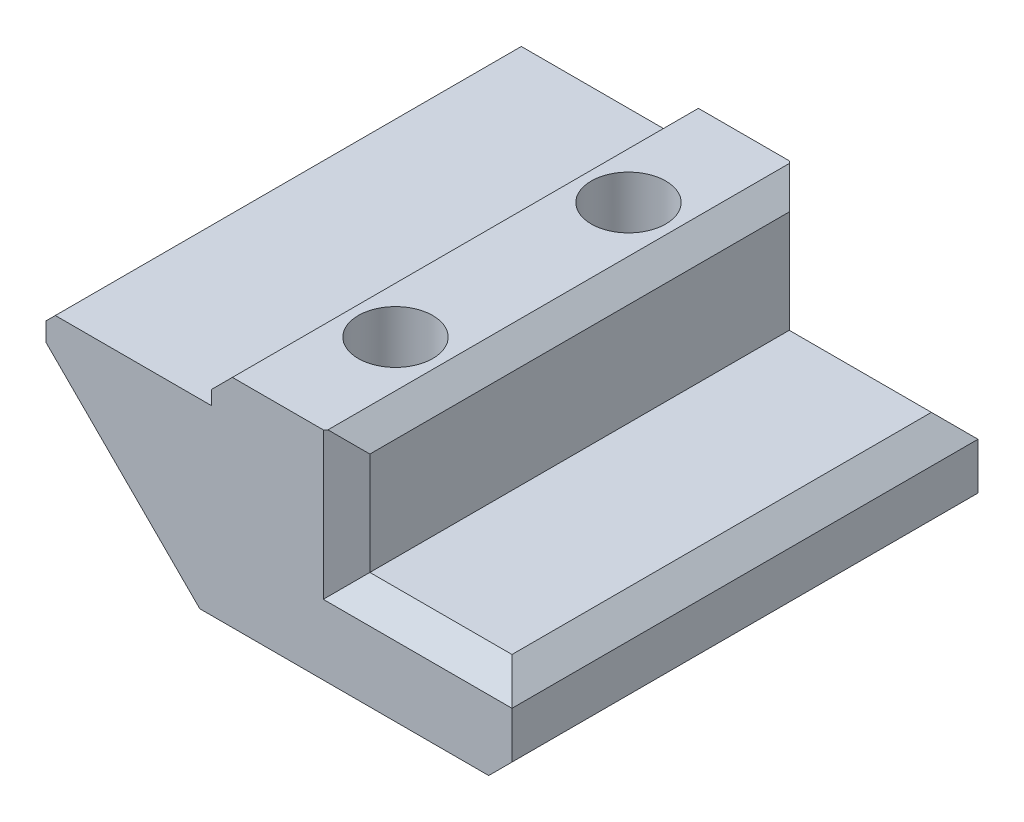
SolidWorks part; units mm, degrees
ref_plane "前视基准面" through (0, 0, 0) normal (0, 0, 1) x (1, 0, 0)
ref_plane "上视基准面" through (0, 0, 0) normal (0, 1, 0) x (1, 0, 0)
ref_plane "右视基准面" through (0, 0, 0) normal (1, 0, 0) x (0, 0, -1)
other "Configuration Table"
sketch "草图1" plane through (0, 0, 0) normal (0, 1, 0) x (1, 0, 0)
  line L1 (0, 0) -> (20, 0)
  line L2 (0, 0) -> (0, 20)
  line L3 (0, 20) -> (20, 20)
  line L4 (20, 0) -> (20, 20)
  dimension "D1" = 20
  dimension "D2" = 20
extrude "凸台-拉伸1" add sketch "草图1" along normal blind 4
sketch "草图2" plane through (0, 4, 0) normal (0, 1, 0) x (1, 0, 0)
  line L0 (0, 0) -> (20, 0) construction
  line L1 (0, 20) -> (12.9, 20)
  line L2 (0, 20) -> (0, 0)
  line L3 (0, 0) -> (12.9, 0)
  line L4 (12.9, 20) -> (12.9, 0)
  line L5 (20, 0) -> (20, 20) construction
  dimension "D1" = 7.1
extrude "凸台-拉伸2" add sketch "草图2" along normal blind 3.8
sketch "草图3" plane through (0, 0, 0) normal (0, -1, 0) x (-1, 0, 0)
  line L0 (0, 20) -> (0, 0) construction
  line L2 (0, 0) -> (-20, 0) construction
  circle A0 centre (-10, 5) radius 1.6
  circle A1 centre (-10, 15) radius 1.6
  dimension "D1" = 3.2
  dimension "D3" = 5
  dimension "D2" = 10
  dimension "D4" = 2
extrude "切除-拉伸1" cut sketch "草图3" against normal through all
sketch "草图4" plane through (0, 7.8, 0) normal (0, 1, 0) x (1, 0, 0)
  line L0 (12.9, 20) -> (0, 20) construction
  line L1 (7.1, 20) -> (12.9, 20)
  line L2 (7.1, 20) -> (7.1, 0)
  line L3 (7.1, 0) -> (12.9, 0)
  line L4 (12.9, 20) -> (12.9, 0)
  line L5 (0, 20) -> (0, 0) construction
  circle A0 centre (10, 15) radius 1.6
  circle A1 centre (10, 5) radius 1.6
  point P6 (10, 20)
  dimension "D1" = 5.8
  dimension "D2" = 10
extrude "凸台-拉伸3" add sketch "草图4" along normal blind 1.5
sketch "草图5" plane through (0, 0, 0) normal (0, -1, 0) x (-1, 0, 0)
  circle A0 centre (-10, 5) radius 3
  circle A1 centre (-10, 15) radius 3
  dimension "D1" = 6
  dimension "D2" = 6
extrude "切除-拉伸3" cut sketch "草图5" against normal blind 2.4
chamfer "倒角3" distance 1.5 angle 45 2 edges at (10, 2.4, -16.6) (10, 2.4, -6.6)
chamfer "倒角1" distance 6.6 angle 45 1 edges at (0, 0, -10)
chamfer "倒角2" distance 1 angle 45 6 edges at (20, 0, -10) (12.9, 6.65, -20) (16.45, 4, -20) (20, 4, -10) (16.45, 4, 0) (12.9, 6.65, 0)
chamfer "倒角4" distance 0.4 angle 45 1 edges at (0, 7.8, -10)
chamfer "倒角5" distance 0.9 angle 45 2 edges at (12.9, 9.3, -10) (7.1, 9.3, -10)
